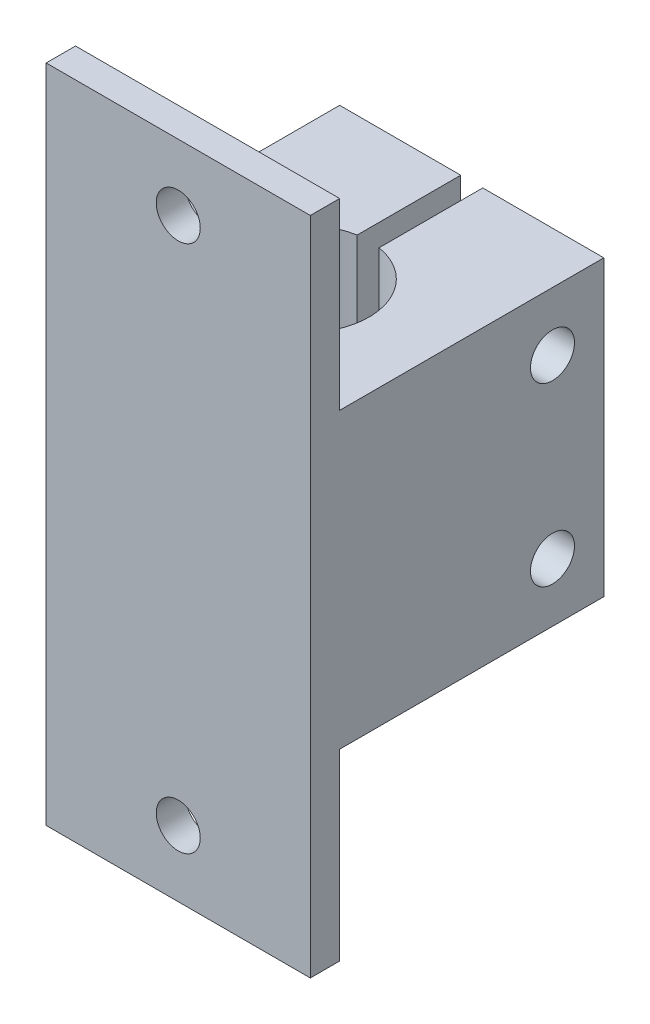
SolidWorks part; units mm, degrees
ref_plane "Front Plane" through (0, 0, 0) normal (0, 0, 1) x (1, 0, 0)
ref_plane "Top Plane" through (0, 0, 0) normal (0, 1, 0) x (1, 0, 0)
ref_plane "Right Plane" through (0, 0, 0) normal (1, 0, 0) x (0, 0, -1)
sketch "Sketch1" plane through (0, 0, 0) normal (0, 1, 0) x (1, 0, 0)
  line L0 (-28.1392, 0) -> (24.5506, 0) construction
  line L1 (0, 16.6044) -> (0, -14.6108) construction
  line L2 (-9, 0) -> (-9, 18)
  line L3 (-9, 18) -> (9, 18)
  line L4 (-9, 0) -> (9, 0)
  line L5 (9, 0) -> (9, 18)
  point P10 (0, 0)
  point P11 (0, 18)
  dimension "D1" = 9
  dimension "D2" = 18
extrude "Boss-Extrude1" add sketch "Sketch1" along normal blind 20
sketch "Sketch2" plane through (0, 20, 0) normal (0, 1, 0) x (1, 0, 0)
  line L0 (-9, 0) -> (9, 0) construction
  line L1 (9, 0) -> (9, 18) construction
  line L2 (0, 18.6431) -> (0, -3.9642) construction
  line L3 (0.75, 10.9371) -> (0.75, 18)
  line L4 (9, 18) -> (-9, 18) construction
  line L5 (0.75, 18) -> (0, 18)
  line L6 (-0.75, 10.9371) -> (-0.75, 18)
  line L7 (-0.75, 18) -> (0, 18)
  circle A0 centre (0, 6.5) radius 4.5
  arc A1 (0.75, 10.9371) -> (-0.75, 10.9371) centre (0, 6.5) cw
  line M7 (9, 18) -> (-9, 18)
  dimension "D1" = 9
  dimension "D2" = 6.5
  dimension "D3" = 9
  dimension "D4" = 9
  dimension "D5" = 0.75
  dimension "D6" = 0.75
extrude "Cut-Extrude1" cut sketch "Sketch2" against normal through all contours A0 L2 A1 | L2 A0 | L2 A0 L3 M7 | L2 L6 A0 M7 region at (0.3756, 20, -14.4895) region at (-0.3756, 20, -14.4895) region at (1.9099, 20, -6.5) region at (-1.9099, 20, -6.5)
sketch "Sketch3" plane through (9, 0, 0) normal (1, 0, 0) x (0, 0, -1)
  line L0 (18, 20) -> (18, 0) construction
  line L1 (0, 20) -> (18, 20) construction
  line L2 (0, 0) -> (18, 0) construction
  circle A0 centre (14.5, 16) radius 1.5
  circle A1 centre (14.5, 4) radius 1.5
  dimension "D1" = 3
  dimension "D2" = 3
  dimension "D3" = 3.5
  dimension "D4" = 3.5
  dimension "D5" = 4
  dimension "D6" = 4
extrude "Cut-Extrude2" cut sketch "Sketch3" against normal through all
sketch "Sketch4" plane through (0, 0, 0) normal (0, 0, 1) x (1, 0, 0)
  line L0 (-16.8576, 10) -> (16.4765, 10) construction
  line L1 (-9, 20) -> (9, 20) construction
  line L2 (0, 26.795) -> (0, -4.8499) construction
  line L4 (-9, 32.5) -> (9, 32.5)
  line L5 (-9, 32.5) -> (-9, -12.5)
  line L6 (-9, -12.5) -> (9, -12.5)
  line L7 (9, 32.5) -> (9, -12.5)
  line L8 (-9, 32.5) -> (9, -12.5) construction
  line L9 (-9, -12.5) -> (9, 32.5) construction
  point P7 (0, 10)
  dimension "D1" = 10
  dimension "D2" = 45
  dimension "D3" = 18
extrude "Boss-Extrude2" add sketch "Sketch4" along normal blind 2
sketch "Sketch5" plane through (0, 0, 2) normal (0, 0, 1) x (1, 0, 0)
  line L0 (9, 32.5) -> (-9, 32.5) construction
  line L3 (-9, 32.5) -> (-9, -12.5) construction
  circle A0 centre (0, 28) radius 1.5
  circle A1 centre (0, -8) radius 1.5
  dimension "D1" = 3
  dimension "D2" = 36
  dimension "D3" = 4.5
  dimension "D4" = 9
extrude "Cut-Extrude3" cut sketch "Sketch5" against normal through all
